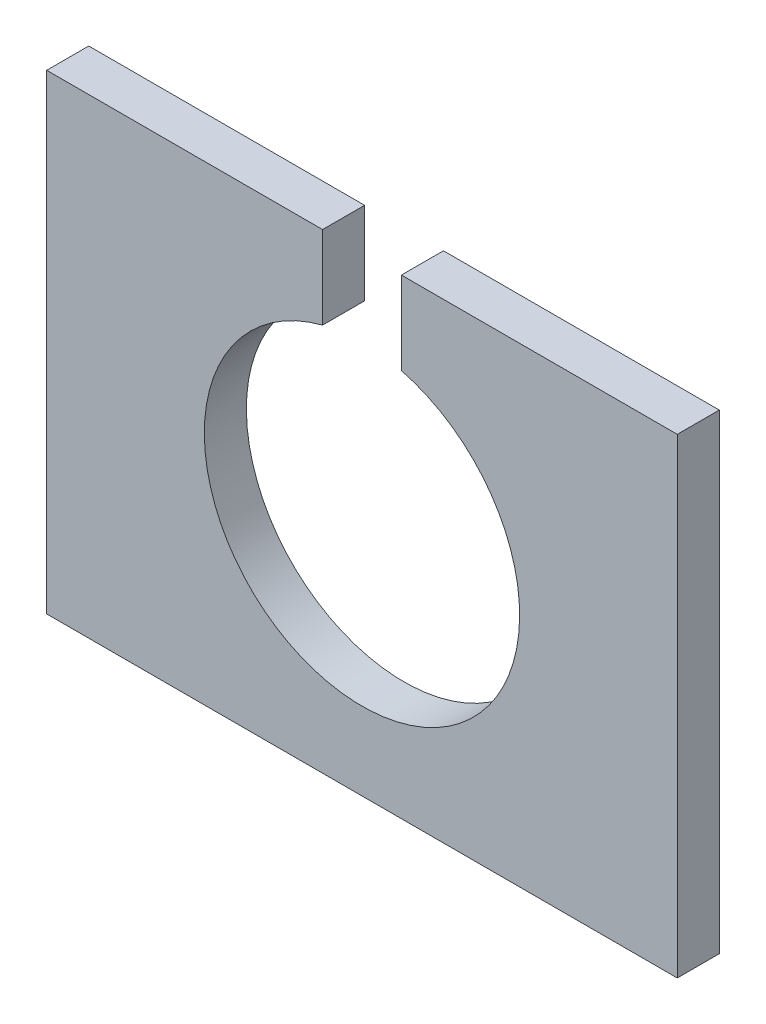
SolidWorks part; units mm, degrees
ref_plane "Front Plane" through (0, 0, 0) normal (0, 0, 1) x (1, 0, 0)
ref_plane "Top Plane" through (0, 0, 0) normal (0, 1, 0) x (1, 0, 0)
ref_plane "Right Plane" through (0, 0, 0) normal (1, 0, 0) x (0, 0, -1)
sketch "Sketch1" plane through (0, 0, 0) normal (0, 0, 1) x (1, 0, 0)
  line L0 (0, 0) -> (38.1, 0)
  line L1 (38.1, 0) -> (38.1, 28.448)
  line L7 (0, 28.448) -> (0, 0)
  line L8 (19.05, 0) -> (19.05, 36.1275) construction
  line L9 (0, 28.448) -> (38.1, 28.448)
  dimension "D1" = 28.448
  dimension "D3" = 38.1
extrude "Boss-Extrude1" add sketch "Sketch1" against normal blind 2.54
sketch "Sketch3" plane through (0, 0, 0) normal (0, 0, 1) x (1, 0, 0)
  line L0 (19.05, 0) -> (19.05, 28.9356) construction
  line L1 (0, 0) -> (38.1, 0) construction
  line L2 (16.6687, 28.448) -> (16.6688, 23.4465)
  line L3 (38.1, 28.448) -> (0, 28.448) construction
  line L4 (16.6687, 28.448) -> (21.4312, 28.448)
  line L5 (21.4312, 28.448) -> (21.4312, 23.4465)
  line L6 (16.6687, 28.448) -> (21.4312, 28.448)
  line L7 (0, 28.448) -> (0, 0) construction
  arc A0 (16.6688, 23.4465) -> (21.4312, 23.4465) centre (19.05, 14.224) ccw
  line M8 (38.1, 28.448) -> (0, 28.448)
  dimension "D1" = 19.05
  dimension "D2" = 14.224
  dimension "D3" = 4.7625
  dimension "D4" = 16.6687
extrude "Cut-Extrude2" cut sketch "Sketch3" against normal up to next contours A0 L0 L6 L2 | L0 A0 L5 M8 region at (15.2183, 15.1017, 0) region at (22.8817, 15.1017, 0)
